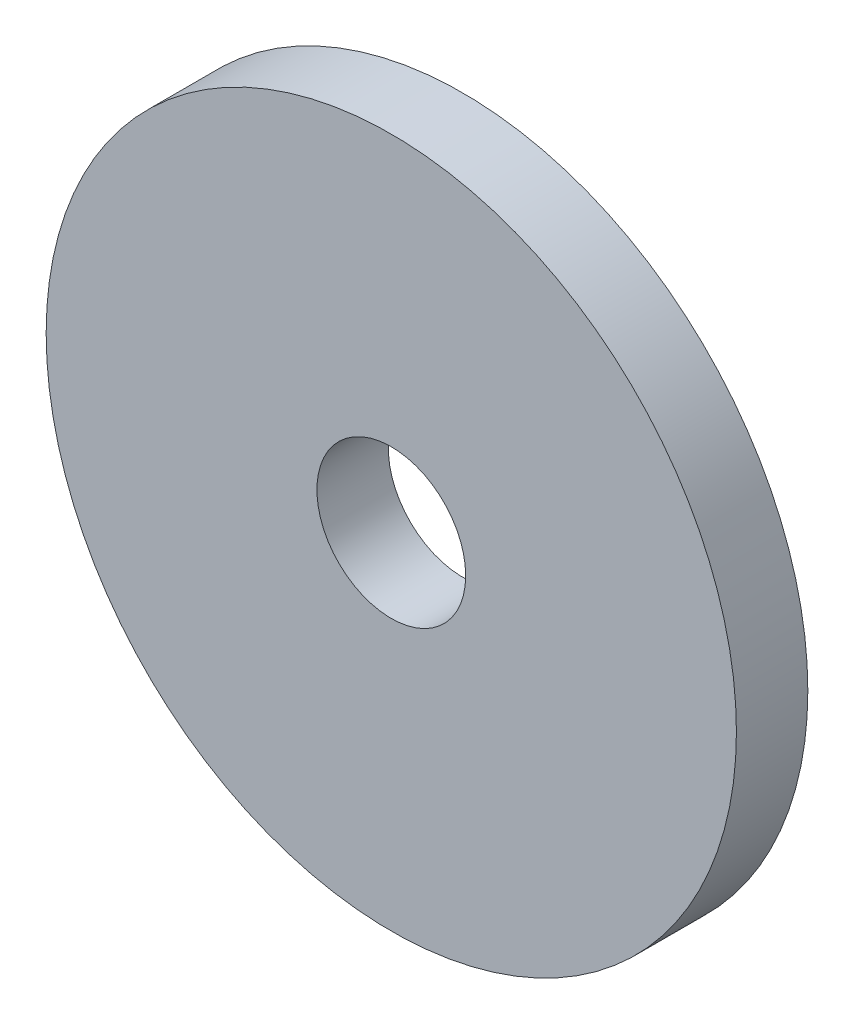
SolidWorks part; units mm, degrees
ref_plane "Front Plane" through (0, 0, 0) normal (0, 0, 1) x (1, 0, 0)
ref_plane "Top Plane" through (0, 0, 0) normal (0, 1, 0) x (1, 0, 0)
ref_plane "Right Plane" through (0, 0, 0) normal (1, 0, 0) x (0, 0, -1)
sketch "Sketch1" plane through (0, 0, 0) normal (0, 0, 1) x (1, 0, 0)
  circle A0 centre (0, 0) radius 14.732
  dimension "D1" = 29.464
extrude "Boss-Extrude1" add sketch "Sketch1" along normal blind 3.048 contours A0
sketch "Sketch2" plane through (0, 0, 3.048) normal (0, 0, 1) x (1, 0, 0)
  circle A0 centre (0, 0) radius 3.175
  dimension "D1" = 6.35
extrude "Cut-Extrude1" cut sketch "Sketch2" against normal blind 3.048
